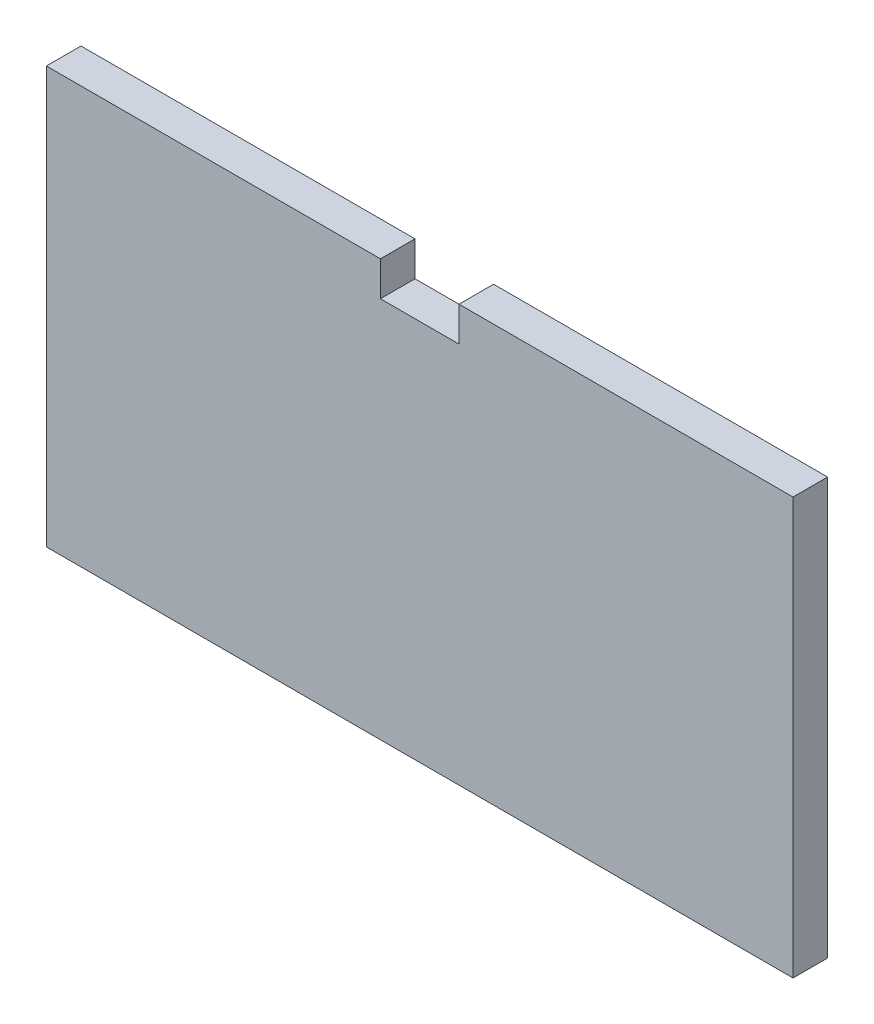
SolidWorks part; units mm, degrees
ref_plane "Front Plane" through (0, 0, 0) normal (0, 0, 1) x (1, 0, 0)
ref_plane "Top Plane" through (0, 0, 0) normal (0, 1, 0) x (1, 0, 0)
ref_plane "Right Plane" through (0, 0, 0) normal (1, 0, 0) x (0, 0, -1)
sketch "Sketch1" plane through (0, 0, 0) normal (0, 0, 1) x (1, 0, 0)
  line L0 (-6.35, 33.655) -> (-6.35, 28.067)
  line L1 (-60.325, -33.655) -> (60.325, -33.655)
  line L2 (-60.325, -33.655) -> (-60.325, 33.655)
  line L3 (-60.325, 33.655) -> (-6.35, 33.655)
  line L4 (60.325, -33.655) -> (60.325, 33.655)
  line L5 (-60.325, -33.655) -> (60.325, 33.655) construction
  line L6 (-60.325, 33.655) -> (60.325, -33.655) construction
  line L7 (-6.35, 28.067) -> (6.35, 28.067)
  line L8 (6.35, 28.067) -> (6.35, 33.655)
  line L9 (6.35, 33.655) -> (60.325, 33.655)
  point P0 (0, 0)
  dimension "D1" = 120.65
  dimension "D2" = 67.31
  dimension "D3" = 5.588
  dimension "D4" = 12.7
extrude "Boss-Extrude1" add sketch "Sketch1" along normal mid plane 5.588
